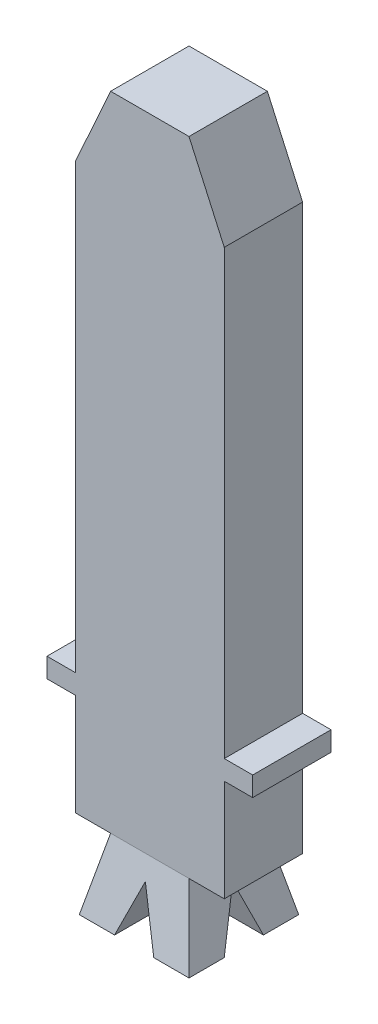
SolidWorks part; units mm, degrees
ref_plane "Front Plane" through (0, 0, 0) normal (0, 0, 1) x (1, 0, 0)
ref_plane "Top Plane" through (0, 0, 0) normal (0, 1, 0) x (1, 0, 0)
ref_plane "Right Plane" through (0, 0, 0) normal (1, 0, 0) x (0, 0, -1)
sketch "Sketch1" plane through (0, 0, 0) normal (0, 0, 1) x (1, 0, 0)
  line L0 (1.9, 0) -> (2.625, 0)
  line L2 (-1.9, 11.3) -> (-1.9, 0)
  line L4 (1.9, 11.3) -> (1.9, 0)
  line L5 (-2.625, 0) -> (-1.9, 0)
  line L6 (-2.625, 0) -> (-2.625, -0.5)
  line L7 (-2.625, -0.5) -> (-1.9, -0.5)
  line L8 (2.625, 0) -> (2.625, -0.5)
  line L9 (1.9, -0.5) -> (2.625, -0.5)
  line L11 (-1.9, -0.5) -> (-1.9, -3.1)
  line L12 (-1.9, -3.1) -> (1.9, -3.1)
  line L13 (1.9, -0.5) -> (1.9, -3.1)
  line L14 (-1, 13.3) -> (1, 13.3)
  line L15 (-1.9, 11.3) -> (-1, 13.3)
  line L16 (1, 13.3) -> (1.9, 11.3)
  point P9 (2.625, -0.25)
  dimension "D2" = 3.8
  dimension "D3" = 1.9
  dimension "D5" = 5.25
  dimension "D6" = 2.625
  dimension "D1" = 2.6
  dimension "D7" = 1.9
  dimension "D8" = 1.9
  dimension "D9" = 0.25
  dimension "D10" = 0.5
  dimension "D11" = 2
  dimension "D13" = 0.9
  dimension "D14" = 3.8
  dimension "D4" = 11.3
  dimension "D12" = 13.3
extrude "Boss-Extrude1" add sketch "Sketch1" along normal blind 2
ref_plane "Plane1" through (0, -4.9, 0) normal (0, -1, 0) x (-1, 0, 0)
sketch "Sketch2" plane through (0, -3.1, 0) normal (0, -1, 0) x (1, 0, 0)
  line L0 (-1.9, 2) -> (1.9, 2) construction
  line L1 (-1, 2) -> (1, 2)
  line L2 (-1, 2) -> (-1, 0)
  line L3 (-1, 0) -> (1, 0)
  line L4 (1, 2) -> (1, 0)
  line L5 (-1.9, 0) -> (1.9, 0) construction
  dimension "D1" = 2
  dimension "D2" = 2
  dimension "D3" = 1
sketch "Sketch3" plane through (0, -4.9, 0) normal (0, -1, 0) x (-1, 0, 0)
  line L1 (-1.4, 0.4) -> (1.4, 0.4)
  line L2 (-1.4, 0.4) -> (-1.4, -2.4)
  line L3 (-1.4, -2.4) -> (1.4, -2.4)
  line L4 (1.4, 0.4) -> (1.4, -2.4)
  dimension "D1" = 2.8
  dimension "D2" = 2.8
  dimension "D3" = 1.4
  dimension "D4" = 0.4
loft "Loft1" add profiles "Sketch2", "Sketch3" connector at (1, -3.1, 2) connector at (1.4, -4.9, 2.4)
ref_plane "Plane2" through (0, 0, 1.8) normal (0, 0, 1) x (1, 0, 0)
sketch "Sketch4" plane through (0, 0, 1.8) normal (0, 0, 1) x (1, 0, 0)
  line L0 (0, -3.6115) -> (-0.5, -4.9)
  line L1 (-1.1, -4.9) -> (1.1, -4.9) construction
  line L2 (-0.5, -4.9) -> (0.5, -4.9)
  line L3 (0.5, -4.9) -> (0, -3.6115)
  dimension "D1" = 0.5
  dimension "D2" = 0.5
  dimension "D3" = 3.6115
ref_plane "Plane3" through (1.8, 0, 0) normal (1, 0, 0) x (0, 0, -1)
sketch "Sketch5" plane through (1.8, 0, -1.8) normal (-1, 0, 0) x (0, 0, 1)
  line L0 (2.8, -3.6115) -> (2.3, -4.9)
  line L1 (1.4, -4.9) -> (4.2, -4.9) construction
  line L2 (2.3, -4.9) -> (3.3, -4.9)
  line L3 (3.3, -4.9) -> (2.8, -3.6115)
  line L4 (1.4, -4.9) -> (4.2, -4.9) construction
extrude "Cut-Extrude1" cut sketch "Sketch4" against normal through all both and the other way through all
extrude "Cut-Extrude2" cut sketch "Sketch5" against normal through all both and the other way through all
equation "\"D3@Sketch1\"=\"D2@Sketch1\"/2"
equation "\"D6@Sketch1\"=\"D5@Sketch1\"/2"
equation "\"D3@Sketch3\"=\"D1@Sketch3\"/2"
equation "\"D4@Sketch3\"=(\"D2@Sketch3\"-2)/2"
